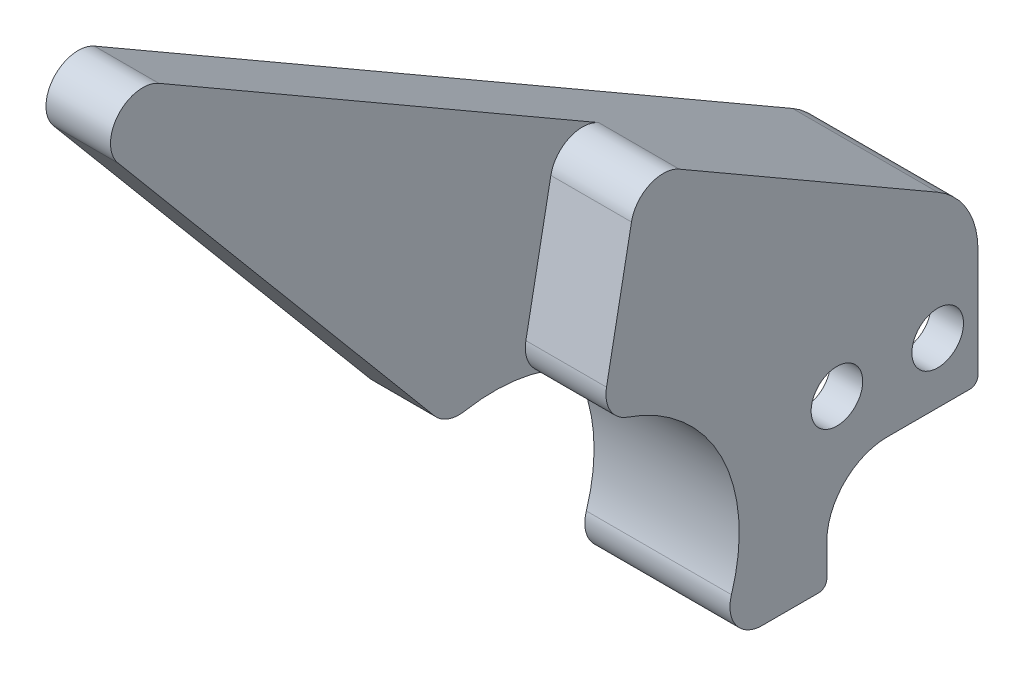
SolidWorks part; units mm, degrees
ref_plane "Front Plane" through (0, 0, 0) normal (0, 0, 1) x (1, 0, 0)
ref_plane "Top Plane" through (0, 0, 0) normal (0, 1, 0) x (1, 0, 0)
ref_plane "Right Plane" through (0, 0, 0) normal (1, 0, 0) x (0, 0, -1)
sketch "Sketch1" plane through (0, 0, 0) normal (1, 0, 0) x (0, 0, -1)
  line L0 (3.175, 12.7) -> (11.1125, 12.7) construction
  line L1 (14.2875, 0) -> (0, 0)
  line L2 (14.2875, 0) -> (14.2875, 17.145)
  line L4 (0, 0) -> (0, 17.145)
  line L5 (-2.6495, -67.6337) -> (6.077, -65.3632) construction
  line L6 (-2.6495, -67.6337) -> (6.077, -65.3632) construction
  line L7 (-17.4737, 7.2462) -> (1.7137, -66.4985) construction
  line L8 (-21.168, 19.6623) -> (-47.0959, 50.5619)
  line L9 (11.1125, 22.6443) -> (-43.8801, 54.3943)
  line L12 (0, 17.145) -> (14.2875, 17.145)
  line L13 (0.635, 15.875) -> (13.6525, 15.875) construction
  line L14 (0.635, 15.875) -> (13.6525, 15.875) construction
  line L15 (2.3813, 3.175) -> (2.3813, 0)
  line L16 (7.1438, 7.9375) -> (14.2875, 7.9375)
  line L17 (-6.736, 0) -> (0, 0)
  line L18 (-49.9397, 6.7592) -> (-17.3951, 61.2854) construction
  line L19 (-20.2993, 19.8883) -> (-12.7193, 59.5063) construction
  line L20 (-12.3332, 36.1807) -> (-15.422, 20.0367)
  circle A0 centre (3.175, 12.7) radius 2.032
  circle A1 centre (11.1125, 12.7) radius 2.032
  circle A2 centre (-17.4737, 7.2462) radius 12.7 construction
  arc A5 (-47.0959, 50.5619) -> (-43.8801, 54.3943) centre (-45.1501, 52.1946) cw
  arc A6 (11.1125, 22.6443) -> (14.2875, 17.145) centre (7.9375, 17.145) cw
  circle A7 centre (7.1438, 3.175) radius 3.5306 construction
  circle A8 centre (7.1438, 3.175) radius 3.5306 construction
  arc A9 (2.3813, 3.175) -> (7.1438, 7.9375) centre (7.1438, 3.175) cw
  arc A10 (-6.736, 0) -> (-21.168, 19.6623) centre (-17.4737, 7.2462) ccw
  arc A11 (-12.7193, 59.5063) -> (-17.3951, 61.2854) centre (-15.214, 59.9836) ccw construction
  point P8 (7.1437, 12.7)
  point P9 (7.1438, 0)
  point P10 (7.1437, 12.7)
  point P11 (7.1438, 0)
  point P18 (1.7137, -66.4985)
  dimension "D1" = 7.9375
  dimension "D3" = 4.064
  dimension "D4" = 12.7
  dimension "D5" = 1.27
  dimension "D6" = 25.4
  dimension "D7" = 120
  dimension "D8" = 2.54
  dimension "D12" = 63.5
  dimension "D11" = 6.35
  dimension "D13" = 4.7625
  dimension "D14" = 12.954
  dimension "D2" = 14.2875
  dimension "D9" = 40
  dimension "D10" = 76.2
  dimension "D15" = 4.7625
extrude "Boss-Extrude1" add sketch "Sketch1" along normal blind 2.54 contours A10 L17 L4 L12 A6 L9 L20 | L15 A9 L16 L2 L12 L4 L1 A1 A0 | A10 L20 L9 A5 L8 region at (0, 11.0438, -6.1349) region at (0, 20.4858, 2.9441) region at (0, 36.9517, 27.5941)
extrude "Boss-Extrude2" add sketch "Sketch1<4>" against normal up to surface (6.35 mm away) contours A10 L17 L4 L12 A6 L9 L20 | A10 L20 L9 A5 L8 region at (0, 20.4858, 2.9441) region at (0, 36.9517, 27.5941)
sketch "Sketch1<4>" plane through (0, 0, 0) normal (1, 0, 0) x (0, 0, -1) same geometry as "Sketch1"
sketch "Sketch4" plane through (-6.35, 0, 0) normal (-1, 0, 0) x (0, 0, 1)
  line L6 (-2.3813, 0) -> (6.736, 0)
  line L7 (-2.3813, 3.175) -> (-2.3813, 0)
  line L8 (-14.2875, 7.9375) -> (-7.1438, 7.9375)
  line L9 (-14.2875, 17.145) -> (-14.2875, 7.9375)
  line L10 (43.8801, 54.3943) -> (-11.1125, 22.6443)
  line L11 (21.168, 19.6623) -> (47.0959, 50.5619)
  line L12 (-2.3813, 0) -> (6.736, 0)
  line L13 (-2.3813, 3.175) -> (-2.3813, 0)
  line L14 (-14.2875, 7.9375) -> (-7.1438, 7.9375)
  line L15 (-14.2875, 17.145) -> (-14.2875, 7.9375)
  line L16 (43.8801, 54.3943) -> (-11.1125, 22.6443)
  line L17 (21.168, 19.6623) -> (47.0959, 50.5619)
  circle A0 centre (-3.175, 12.7) radius 2.032 construction
  circle A1 centre (-11.1125, 12.7) radius 2.032 construction
  circle A2 centre (-3.175, 12.7) radius 2.032
  circle A3 centre (-11.1125, 12.7) radius 2.032
  arc A4 (21.168, 19.6623) -> (6.736, 0) centre (17.4737, 7.2462) ccw
  arc A5 (-2.3813, 3.175) -> (-7.1438, 7.9375) centre (-7.1438, 3.175) ccw
  arc A6 (-11.1125, 22.6443) -> (-14.2875, 17.145) centre (-7.9375, 17.145) ccw
  arc A7 (47.0959, 50.5619) -> (43.8801, 54.3943) centre (45.1501, 52.1946) ccw
  arc A8 (21.168, 19.6623) -> (6.736, 0) centre (17.4737, 7.2462) ccw
  arc A9 (-2.3813, 3.175) -> (-7.1438, 7.9375) centre (-7.1438, 3.175) ccw
  arc A10 (-11.1125, 22.6443) -> (-14.2875, 17.145) centre (-7.9375, 17.145) ccw
  arc A11 (47.0959, 50.5619) -> (43.8801, 54.3943) centre (45.1501, 52.1946) ccw
  dimension "D1" = 0
extrude "Boss-Extrude3" add sketch "Sketch4" along normal blind 2.54
sketch "Sketch5" plane through (2.54, 0, 0) normal (1, 0, 0) x (0, 0, -1)
  line L0 (-12.3332, 36.1807) -> (-15.422, 20.0367) construction
  line L1 (-12.3332, 36.1807) -> (-15.422, 20.0367)
  line L8 (-6.736, 0) -> (2.3813, 0)
  line L9 (2.3813, 0) -> (2.3813, 3.175)
  line L10 (7.1438, 7.9375) -> (14.2875, 7.9375)
  line L11 (14.2875, 7.9375) -> (14.2875, 17.145)
  line L12 (11.1125, 22.6443) -> (-43.8801, 54.3943)
  line L13 (-47.0959, 50.5619) -> (-21.168, 19.6623)
  line L14 (-6.736, 0) -> (2.3813, 0)
  line L15 (2.3813, 0) -> (2.3813, 3.175)
  line L16 (7.1438, 7.9375) -> (14.2875, 7.9375)
  line L17 (14.2875, 7.9375) -> (14.2875, 17.145)
  line L18 (11.1125, 22.6443) -> (-43.8801, 54.3943)
  line L19 (-47.0959, 50.5619) -> (-21.168, 19.6623)
  arc A4 (-6.736, 0) -> (-21.168, 19.6623) centre (-17.4737, 7.2462) ccw
  arc A5 (7.1438, 7.9375) -> (2.3813, 3.175) centre (7.1438, 3.175) ccw
  arc A6 (14.2875, 17.145) -> (11.1125, 22.6443) centre (7.9375, 17.145) ccw
  arc A7 (-43.8801, 54.3943) -> (-47.0959, 50.5619) centre (-45.1501, 52.1946) ccw
  arc A8 (-6.736, 0) -> (-21.168, 19.6623) centre (-17.4737, 7.2462) ccw
  arc A9 (7.1438, 7.9375) -> (2.3813, 3.175) centre (7.1438, 3.175) ccw
  arc A10 (14.2875, 17.145) -> (11.1125, 22.6443) centre (7.9375, 17.145) ccw
  arc A11 (-43.8801, 54.3943) -> (-47.0959, 50.5619) centre (-45.1501, 52.1946) ccw
  arc M11 (-21.168, 19.6623) -> (-6.736, 0) centre (-17.4737, 7.2462) cw
  line M18 (11.1125, 22.6443) -> (-43.8801, 54.3943)
  arc M19 (-43.8801, 54.3943) -> (-47.0959, 50.5619) centre (-45.1501, 52.1946) ccw
  line M20 (-47.0959, 50.5619) -> (-21.168, 19.6623)
  dimension "D1" = 0
extrude "Cut-Extrude2" cut sketch "Sketch5" against normal blind 6.35 contours L1 M18 M19 M20 M11 region at (2.54, 36.9517, 27.5941)
fillet "Fillet1" radius 2.54 4 edges at (-3.175, 0, 6.736) (-0.635, 36.1807, 12.3332) (-0.635, 20.0367, 15.422) (-6.35, 19.6623, 21.168)
fillet "Fillet2" radius 0.635 6 edges at (-3.175, 0, 0) (-3.175, 17.145, -14.2875) (-7.62, 0, -2.3813) (-7.62, 7.9375, -14.2875) (1.27, 7.9375, -14.2875) (1.27, 0, -2.3813)
